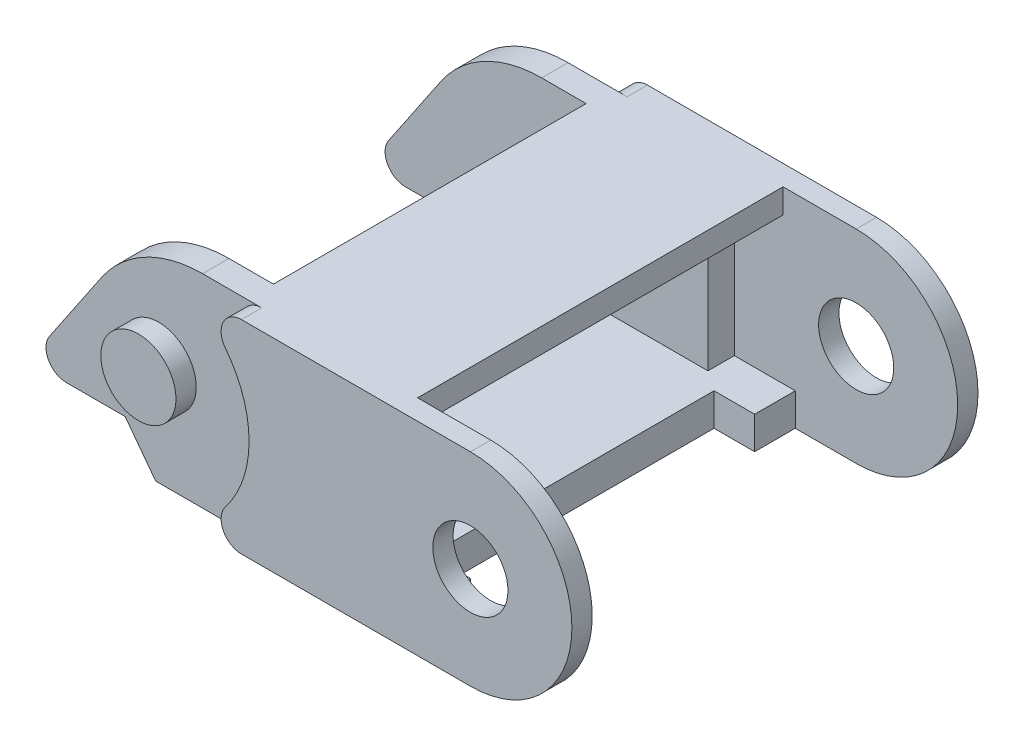
SolidWorks part; units mm, degrees
material "PLA+"
ref_plane "Front Plane" through (0, 0, 0) normal (0, 0, 1) x (1, 0, 0)
ref_plane "Top Plane" through (0, 0, 0) normal (0, 1, 0) x (1, 0, 0)
ref_plane "Right Plane" through (0, 0, 0) normal (1, 0, 0) x (0, 0, -1)
sketch "Sketch3" plane through (0, 0, 0) normal (0, 1, 0) x (1, 0, 0)
  line L0 (4, 7) -> (4, 10)
  line L1 (4, -10) -> (-4, -10)
  line L2 (4, -10) -> (4, -7)
  line L3 (4, 10) -> (-4, 10)
  line L4 (-4, -10) -> (-4, 10)
  line L5 (4, -10) -> (-4, 10) construction
  line L6 (4, 10) -> (-4, -10) construction
  line L7 (4, 7) -> (2, 7)
  line L8 (2, 7) -> (2, -7)
  line L9 (2, -7) -> (4, -7)
  point P0 (0, 0)
  dimension "D1" = 20
  dimension "D2" = 8
  dimension "D3" = 6
  dimension "D4" = 3
  dimension "D5" = 3
extrude "Base" add sketch "Sketch3" along normal blind 1.6
sketch "Sketch4" plane through (0, 0, 10) normal (0, 0, 1) x (1, 0, 0)
  line L0 (-4, 0) -> (4, 0) construction
  line L1 (-4.2765, 0) -> (7, 0)
  line L2 (7, 10) -> (-4.2765, 10)
  arc A0 (-5.0648, 1.6154) -> (-5.0648, 8.3846) centre (-9.4, 5) ccw
  arc A1 (7, 0) -> (7, 10) centre (7, 5) ccw
  circle A2 centre (7, 5) radius 1.85
  arc A3 (-4.2765, 0) -> (-5.0648, 1.6154) centre (-4.2765, 1) cw
  arc A4 (-4.2765, 10) -> (-5.0648, 8.3846) centre (-4.2765, 9) ccw
  circle A5 centre (-9.4, 5) radius 1.85
  point P13 (12, 5)
  point P15 (-7.1087, 0)
  line M3 (4, 0) -> (4, 1.6)
  line M4 (4, 1.6) -> (-4, 1.6)
  line M5 (-4, 1.6) -> (-4, 0)
  dimension "D1" = 10
  dimension "D2" = 11
  dimension "D3" = 3.7
  dimension "D6" = 1
  dimension "D7" = 3.7
  dimension "D4" = 16.4
  dimension "D5" = 10
extrude "OneSide" add sketch "Sketch4" against normal blind 1 contours L2 A4 A0 A3 L1 A1 A2 M5 M4 M3 region at (3.2287, 5.4099, 10)
sketch "Sketch5" plane through (0, 0, 9) normal (0, 0, -1) x (-1, 0, 0)
  line L0 (-1, 10) -> (-1, 0)
  line L2 (-4, 0) -> (4, 0) construction
  line L3 (-1, 0) -> (9.5, 0)
  line L4 (9.5, 0) -> (11, 2)
  line L5 (11, 2) -> (13.9, 2)
  line L6 (14.7285, 3.5599) -> (12.1607, 7.3596)
  line L7 (7.1895, 10) -> (-1, 10)
  line L8 (-4, 1.6) -> (-4, 0) construction
  line L9 (-7, 10) -> (4.2765, 10) construction
  arc A1 (14.7285, 3.5599) -> (13.9, 2) centre (13.9, 3) cw
  arc A3 (12.1607, 7.3596) -> (7.1895, 10) centre (7.1895, 4) ccw
  arc A4 (-7, 10) -> (-7, 0) centre (-7, 5) ccw construction
  circle A5 centre (9.35, 5) radius 1.85
  circle A6 centre (-7, 5) radius 1.85 construction
  point P14 (-12, 5)
  point P18 (12.45, 2)
  dimension "D4" = 1
  dimension "D7" = 6
  dimension "D5" = 3.7
  dimension "D9" = 16.35
  dimension "D1" = 11
  dimension "D2" = 13.5
  dimension "D3" = 2
  dimension "D6" = 15
  dimension "D8" = 5
  dimension "D10" = 3.65
extrude "AnotherSide" add sketch "Sketch5" along normal blind 1.3 contours L6 A3 L7 L0 L3 L4 L5 A1
extrude "Pin" add sketch "Sketch5<3>" against normal blind 1 contours A5 region at (-9.35, 5, 9)
sketch "Sketch5<3>" plane through (0, 0, 9) normal (0, 0, -1) x (-1, 0, 0) same geometry as "Sketch5"
mirror "Mirror1" about plane through (0, 0, 0) normal (0, 0, 1) of "Pin", "AnotherSide", "OneSide"
sketch "Sketch6" plane through (0, 10, 0) normal (0, 1, 0) x (1, 0, 0)
  line L0 (-5, 8.5479) -> (-5, -8.5257)
  line L1 (-5, -8.5257) -> (3.4, -9.5205)
  line L2 (3.4, -9.5205) -> (3.4, 9.5887)
  line L3 (3.4, 9.5887) -> (-5, 8.5479)
  dimension "D1" = 17
  dimension "D2" = 8.4
extrude "Boss-Extrude9" add sketch "Sketch6" against normal blind 1.2
ref_plane "Plane1" through (0, 5, 0) normal (0, 1, 0) x (1, 0, 0)
ref_plane "Plane2" through (-0.8, 0, 0) normal (-1, 0, 0) x (0, 0, 1)
sketch "ForCable" plane through (0, 5, 0) normal (0, 1, 0) x (1, 0, 0)
  line L3 (0, -5.2) -> (-2.5008, -5.2) construction
  line L4 (0, -0.2) -> (-2.5008, -0.2) construction
  line L5 (-7.1895, -7.7) -> (-5, -7.7) construction
  point P0 (0, -0.2)
  point P1 (0, -5.2)
  dimension "D1" = 2.5
  dimension "D2" = 5
